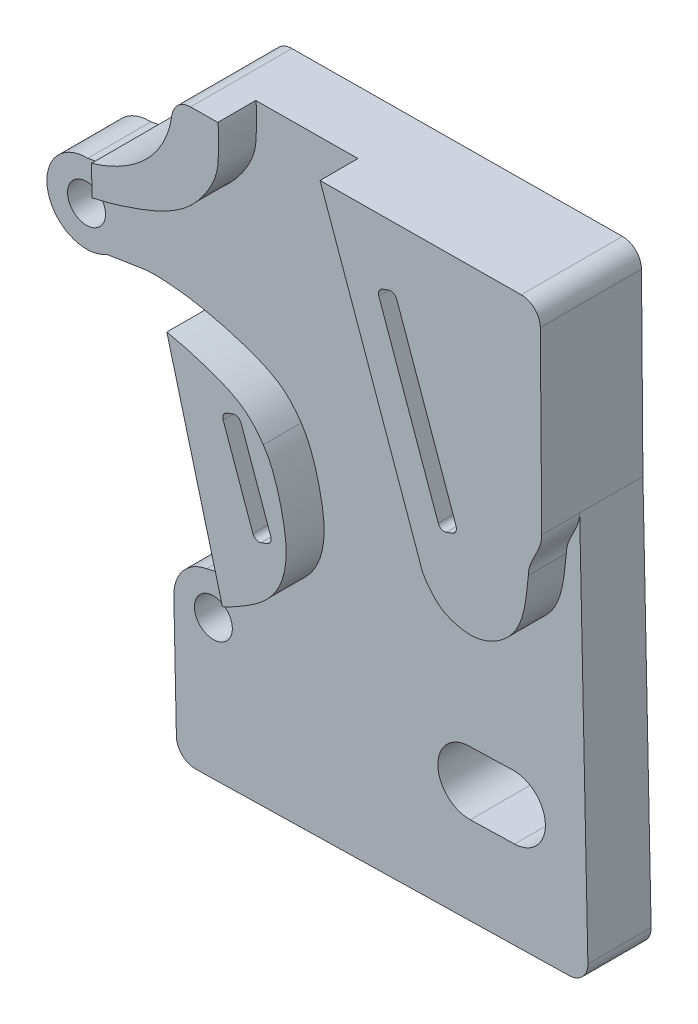
SolidWorks part; units mm, degrees
ref_plane "Front Plane" through (0, 0, 0) normal (0, 0, 1) x (1, 0, 0)
ref_plane "Top Plane" through (0, 0, 0) normal (0, 1, 0) x (1, 0, 0)
ref_plane "Right Plane" through (0, 0, 0) normal (1, 0, 0) x (0, 0, -1)
sketch "Sketch1" plane through (0, 0, 0) normal (0, 0, 1) x (1, 0, 0)
  line L0 (2140.6428, 750.4079) -> (2166.6593, 794.2729) construction
  line L1 (2137.244, 750.2857) -> (2104.7777, 750.2857) construction
  line L2 (2104.7777, 750.2857) -> (2104.7777, 761.3075) construction
  line L3 (2104.7777, 750.2857) -> (2104.7777, 740.6606) construction
  line L4 (2085.9672, 760.4603) -> (2084.4125, 750.5819)
  line L5 (2085.9672, 760.4603) -> (2084.4125, 750.5819)
  line L6 (2078.7482, 737.3813) -> (2082.3736, 761.0279)
  line L7 (2161.0512, 806.6326) -> (2160.3436, 802.0176)
  line L8 (2088.4669, 800.7703) -> (2091.1369, 819.8779)
  line L9 (2091.1369, 819.8779) -> (2092.7964, 831.7535)
  line L10 (2092.7964, 831.7535) -> (2150.3972, 823.7045)
  line L11 (2088.4669, 800.7703) -> (2082.3736, 761.0279)
  line L12 (2085.9672, 760.4603) -> (2105.81, 757.3374)
  line L13 (2099.7777, 753.2252) -> (2092.8629, 754.3135)
  line L14 (2103.3791, 791.2249) -> (2117.0445, 817.9318)
  line L15 (2105.73, 784.8426) -> (2127.2965, 826.9912)
  line L16 (2156.3214, 790.8161) -> (2162.3429, 789.0505)
  line L17 (2164.2082, 801.0793) -> (2166.857, 800.2069)
  line L18 (2133.9903, 759.5105) -> (2142.1174, 756.2484)
  line L19 (2084.4125, 750.5819) -> (2104.2553, 747.459)
  line L20 (2078.7482, 737.3813) -> (2147.4438, 726.849)
  line L21 (2103.3791, 791.2249) -> (2100.7084, 792.5915)
  line L22 (2105.81, 757.3374) -> (2104.2553, 747.459)
  line L23 (2147.4438, 726.849) -> (2178.7845, 722.0439)
  line L24 (2178.7845, 722.0439) -> (2194.4276, 824.0736)
  line L25 (2194.4276, 824.0736) -> (2094.8739, 839.337)
  line L26 (2150.3972, 823.7045) -> (2193.4487, 817.6887)
  line L29 (2082.3736, 761.0279) -> (2091.2526, 759.6666)
  line L31 (2178.7572, 826.4761) -> (2163.1142, 724.4464)
  line L32 (2117.0445, 817.9318) -> (2114.3738, 819.2984)
  line L33 (2100.7084, 792.5915) -> (2114.3738, 819.2984)
  line L34 (2134.9525, 787.0703) -> (2127.6643, 772.8266)
  line L35 (2134.9525, 787.0703) -> (2137.6231, 785.7038)
  line L36 (2127.6643, 772.8266) -> (2130.3349, 771.4601)
  line L37 (2137.6231, 785.7038) -> (2130.3349, 771.4601)
  line L38 (2143.0764, 727.5186) -> (2146.6712, 750.9653)
  line L39 (2146.9992, 791.1891) -> (2133.9903, 759.5105)
  circle A0 centre (2140.244, 750.2857) radius 3
  circle A1 centre (2166.2253, 793.9711) radius 3
  circle A2 centre (2099.7777, 753.2252) radius 5
  circle A3 centre (2140.244, 750.2857) radius 6.25
  circle A4 centre (2166.2253, 793.9711) radius 6.2677
  circle A6 centre (2092.8629, 754.3135) radius 5
  spline S0 degree 3 poles (2156.3214, 790.8161) (2154.9611, 791.116) (2152.7062, 791.2812) (2149.5865, 791.3474) (2146.8785, 791.1975) (2143.7159, 790.9029) (2139.219, 790.1349) (2134.311, 788.8848) (2131.695, 786.3663) (2130.8449, 785.4344) knots 0 0 0 0 0.154101 0.251758 0.347212 0.456074 0.604817 0.858224 1 1 1 1
  spline S1 degree 3 poles (2130.8449, 785.4344) (2129.9714, 784.4542) (2128.475, 782.0596) (2127.0774, 778.6725) (2125.9844, 775.3895) (2125.3258, 772.1393) (2125.542, 768.5182) (2127.3532, 764.5187) (2130.5917, 761.7203) (2132.7166, 760.1927) (2133.8486, 759.4289) (2133.9903, 759.5105) knots 0 0 0 0 0.128105 0.274506 0.357519 0.466462 0.597635 0.704104 0.890824 0.985507 1 1 1 1
  spline S2 degree 3 poles (2105.73, 784.8426) (2105.33, 783.8518) (2104.037, 782.3646) (2101.9508, 780.7068) (2099.3994, 780.0442) (2095.1305, 779.9186) (2089.1327, 784.9378) (2089.6415, 790.9676) (2089.7019, 793.9711) knots 0 0 0 0 0.114066 0.211795 0.282399 0.395921 0.665472 1 1 1 1
  spline S3 degree 3 poles (2089.7019, 793.9711) (2089.889, 795.4303) (2088.8711, 797.5572) (2088.3306, 799.7953) (2088.4669, 800.7703) knots 0 0 0 0 0.60138 1 1 1 1
  spline S4 degree 3 poles (2143.2778, 824.6994) (2142.8821, 823.5079) (2142.7945, 821.4216) (2142.2654, 817.8271) (2143.5371, 813.9747) (2145.9637, 810.1359) (2149.8914, 806.8866) (2155.913, 803.7019) (2160.8905, 801.5684) (2164.2082, 801.0793) knots 0 0 0 0 0.103698 0.174611 0.300875 0.430855 0.551223 0.721505 1 1 1 1
  spline S5 degree 3 poles (2150.3972, 823.7045) (2149.7385, 820.6997) (2151.3813, 811.1479) (2160.6347, 806.1441) (2166.2253, 804.9377) knots 0 0 0 0 0.341843 1 1 1 1
  spline S7 degree 3 poles (2133.9903, 759.5105) (2131.4038, 767.3656) (2133.7537, 781.4418) (2143.7414, 789.0768) (2146.9992, 791.1891) knots 0 0 0 0 0.680912 1 1 1 1
  dimension "D2" = 90
  dimension "D3" = 90
  dimension "D11" = 6
  dimension "D12" = 6
  dimension "D1" = 51
  dimension "D4" = 90
  dimension "D5" = 3
  dimension "D6" = 5
  dimension "D7" = 30
  dimension "D8" = 25
  dimension "D9" = 3
  dimension "D10" = 16
extrude "Boss-Extrude6" add sketch "Sketch1" along normal blind 10 contours A6 L12 L4 L19 | A2 L19 L22 L12 | S3 S2 L15 L10 L9 L8 | S5 L10 S4 L17 | S1 S7 S0 | A3 A0 | A4 A1 | S7 A3 S1 S0 A4 S4 L10 L15 S2 S3 L11 L6 L20 L23 L31 L26 S5 L7 L12 L22 L19 L4 | S7 L39 region at (2087.2469, 755.1974, 0) region at (2103.1628, 757.6256, 0) region at (2118.6151, 772.2393, 0) region at (2103.34, 809.0304, 0) region at (2135.0892, 747.0746, 0) region at (2125.841, 771.2854, 0) region at (2150.0403, 813.4377, 0) region at (2160.5794, 796.2555, 0)
extrude "Boss-Extrude7" add sketch "Sketch1<12>" against normal blind 6 contours S3 S2 L15 L10 L9 L8 | S5 L10 S4 L17 | S1 S7 S0 | S7 L39 region at (2103.34, 809.0304, 0) region at (2125.841, 771.2854, 0) region at (2150.0403, 813.4377, 0)
sketch "Sketch1<12>" plane through (0, 0, 0) normal (0, 0, 1) x (1, 0, 0) same geometry as "Sketch1"
fillet "Fillet1" radius 1 8 edges at (2137.6231, 785.7038, 2) (2127.6643, 772.8266, 2) (2130.3349, 771.4601, 2) (2134.9525, 787.0703, 2) (2117.0445, 817.9318, 2) (2114.3738, 819.2984, 2) (2103.3791, 791.2249, 2) (2100.7084, 792.5915, 2)
fillet "Fillet3" radius 3 5 edges at (2150.3972, 823.7045, 2) (2160.3436, 802.0176, 5) (2143.0764, 727.5186, 5) (2078.7482, 737.3813, 5) (2092.7964, 831.7535, 2)
move or copy body "Body-Move/Copy1" bodies to move or copy 115 copy no rotation origin (2065.8546, -135.4033, 2) rotation axis (0.0654, 0.9979, 0) rotation angle 180
